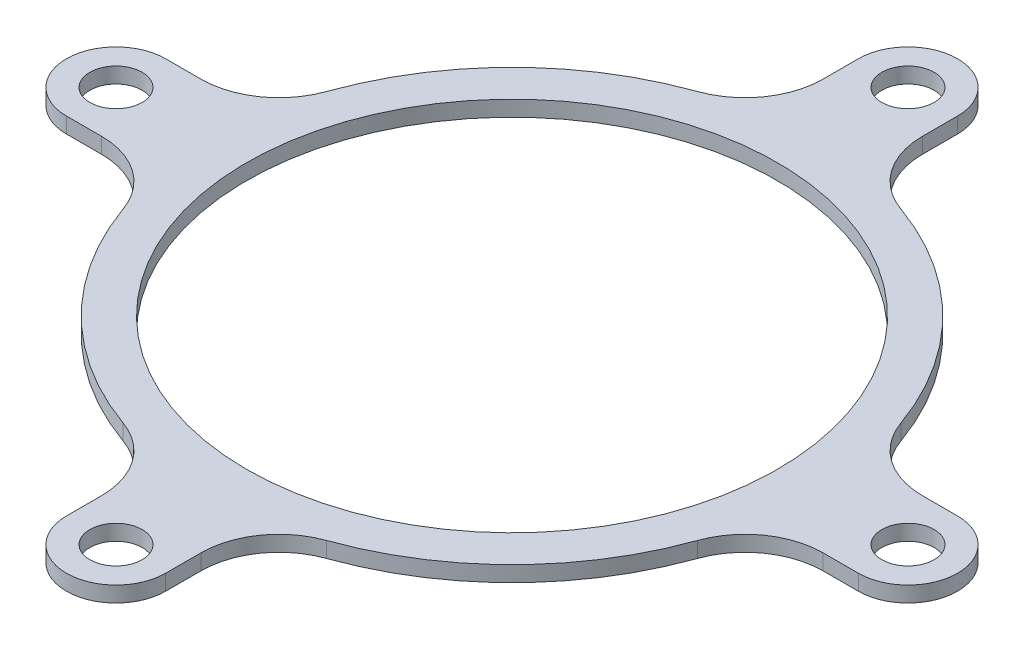
SolidWorks part; units mm, degrees
ref_plane "Front Plane" through (0, 0, 0) normal (0, 0, 1) x (1, 0, 0)
ref_plane "Top Plane" through (0, 0, 0) normal (0, 1, 0) x (1, 0, 0)
ref_plane "Right Plane" through (0, 0, 0) normal (1, 0, 0) x (0, 0, -1)
sketch "Sketch1" plane through (0, 0, 0) normal (0, 1, 0) x (1, 0, 0)
  circle A0 centre (0, 0) radius 34
  circle A1 centre (0, 0) radius 39
  dimension "innerDiam" = 68
  dimension "outerDiam" = 78
extrude "Boss-Extrude1" add sketch "Sketch1" along normal mid plane 2
sketch "Sketch2" plane through (0, 1, 0) normal (0, 1, 0) x (1, 0, 0)
  line L0 (0, 0) -> (0, 38.8704) construction
  line L1 (-6.35, 46.1917) -> (-6.35, 50.7)
  line L2 (6.35, 50.7) -> (6.35, 46.1917)
  arc A0 (-6.35, 50.7) -> (6.35, 50.7) centre (0, 50.7) cw
  arc A1 (6.35, 46.1917) -> (13.0133, 36.7649) centre (16.35, 46.1917) ccw
  circle A2 centre (0, 0) radius 39 construction
  arc A3 (-6.35, 46.1917) -> (-13.0133, 36.7649) centre (-16.35, 46.1917) cw
  arc A4 (13.0133, 36.7649) -> (-13.0133, 36.7649) centre (0, 0) ccw
  circle A5 centre (0, 0) radius 50.7 construction
  circle A6 centre (0, 50.7) radius 3.35
  dimension "supportsDiam" = 101.4
  dimension "rodDiam" = 6.7
  dimension "D3" = 3
  dimension "D4" = 10
extrude "Boss-Extrude2" add sketch "Sketch2" against normal up to surface (2 mm away) up to face at (0, -1, 39)
pattern_circular "CirPattern1" count 4 over 360 about axis through (0, 1, 0) along (0, -1, 0) of "Boss-Extrude2" reverse direction yes
